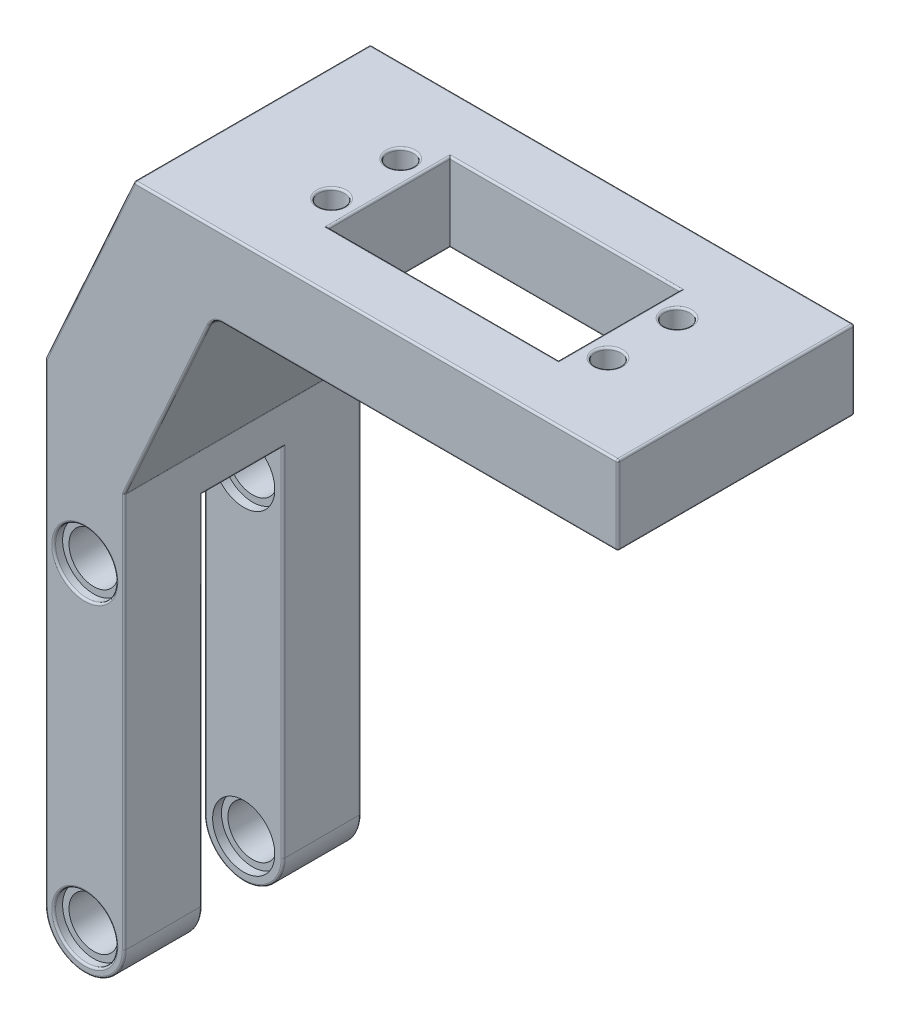
SolidWorks part; units mm, degrees
ref_plane "前视基准面" through (0, 0, 0) normal (0, 0, 1) x (1, 0, 0)
ref_plane "上视基准面" through (0, 0, 0) normal (0, 1, 0) x (1, 0, 0)
ref_plane "右视基准面" through (0, 0, 0) normal (1, 0, 0) x (0, 0, -1)
other "Configuration Table"
sketch "草图1" plane through (0, 0, 0) normal (0, 0, 1) x (1, 0, 0)
  line L1 (-4, -36) -> (4, -36)
  line L2 (-4, -36) -> (-4, 36)
  line L3 (-4, 36) -> (4, 36)
  line L4 (4, -36) -> (4, 36)
  line L5 (-4, -36) -> (4, 36) construction
  line L6 (-4, 36) -> (4, -36) construction
  line L7 (4, 36) -> (54, 36)
  line L8 (4, 36) -> (4, 28)
  line L9 (4, 28) -> (54, 28)
  line L10 (54, 36) -> (54, 28)
  point P0 (0, 0)
  dimension "D1" = 8
  dimension "D2" = 72
  dimension "D3" = 8
  dimension "D4" = 50
extrude "凸台-拉伸1" add sketch "草图1" along normal mid plane 24 contours L1 L4 L3 L2 | L10 L7 L4 L9 region at (0, 0, 0) region at (29, 32, 0)
sketch "草图2" plane through (0, -36, 0) normal (0, -1, 0) x (1, 0, 0)
  line L0 (4, 12) -> (4, -12) construction
  line L1 (-4, -4.1) -> (4, -4.1)
  line L2 (-4, -4.1) -> (-4, 4.1)
  line L3 (-4, 4.1) -> (4, 4.1)
  line L4 (4, -4.1) -> (4, 4.1)
  line L5 (-4, -4.1) -> (4, 4.1) construction
  line L6 (-4, 4.1) -> (4, -4.1) construction
  point P0 (0, 0)
  dimension "D1" = 8.2
extrude "切除-拉伸1" cut sketch "草图2" against normal blind 40.1
sketch "草图3" plane through (0, 0, 0) normal (0, 0, 1) x (1, 0, 0)
  line L0 (-4, -36) -> (4, -36) construction
  circle A0 centre (0, 0) radius 2.5
  circle A1 centre (0, -32) radius 2.5
  dimension "D1" = 5
  dimension "D2" = 4
  dimension "D3" = 32
extrude "切除-拉伸2" cut sketch "草图3" against normal mid plane 40.1
sketch "草图4" plane through (0, 0, 12) normal (0, 0, 1) x (1, 0, 0)
  circle A0 centre (0, 0) radius 3.15
  circle A1 centre (0, -32) radius 3.15
  dimension "D1" = 6.3
extrude "切除-拉伸3" cut sketch "草图4" against normal blind 0.9
extrude "切除-拉伸4" cut sketch "草图4<2>" along normal blind 0.9 from surface starting at face at (2.5, 0, 4.1)
sketch "草图4<2>" plane through (0, 0, 12) normal (0, 0, 1) x (1, 0, 0) same geometry as "草图4"
extrude "切除-拉伸5" cut sketch "草图4<3>" against normal blind 0.9 from surface starting at face at (-2.5, 0, -4.1)
sketch "草图4<3>" plane through (0, 0, 12) normal (0, 0, 1) x (1, 0, 0) same geometry as "草图4"
extrude "切除-拉伸6" cut sketch "草图4<4>" along normal blind 0.9 from surface starting at face at (2.5, 0, -12)
sketch "草图4<4>" plane through (0, 0, 12) normal (0, 0, 1) x (1, 0, 0) same geometry as "草图4"
sketch "草图5" plane through (0, 36, 0) normal (0, 1, 0) x (1, 0, 0)
  line L0 (30.5, 0) -> (24, 0) construction
  line L1 (42.15, -6.15) -> (18.85, -6.15)
  line L2 (42.15, -6.15) -> (42.15, 6.15)
  line L3 (42.15, 6.15) -> (18.85, 6.15)
  line L4 (18.85, -6.15) -> (18.85, 6.15)
  line L5 (42.15, -6.15) -> (18.85, 6.15) construction
  line L6 (42.15, 6.15) -> (18.85, -6.15) construction
  line L7 (-4, -12) -> (-4, 12) construction
  point P0 (30.5, 0)
  dimension "D1" = 23.3
  dimension "D2" = 12.3
  dimension "D3" = 6.5
  dimension "D4" = 6.5
  dimension "D5" = 28
extrude "切除-拉伸7" cut sketch "草图5" against normal blind 8
sketch "草图6" plane through (0, 28, 0) normal (0, -1, 0) x (1, 0, 0)
  line L1 (16.5, 3.5) -> (44.5, 3.5) construction
  line L2 (16.5, 3.5) -> (16.5, -3.5) construction
  line L3 (16.5, -3.5) -> (44.5, -3.5) construction
  line L4 (44.5, 3.5) -> (44.5, -3.5) construction
  line L5 (16.5, 3.5) -> (44.5, -3.5) construction
  line L6 (16.5, -3.5) -> (44.5, 3.5) construction
  circle A0 centre (44.5, 3.5) radius 1.3
  circle A1 centre (44.5, -3.5) radius 1.3
  circle A2 centre (16.5, 3.5) radius 1.3
  circle A3 centre (16.5, -3.5) radius 1.3
  point P0 (30.5, 0)
  dimension "D3" = 2.6
  dimension "D1" = 28
  dimension "D2" = 7
extrude "切除-拉伸8" cut sketch "草图6" against normal blind 8
chamfer "倒角1" distance 20 distance2 9 1 edges at (4, 28, 0) first distance on face at (4, -9.975, 0)
chamfer "倒角2" distance 9 distance2 20 1 edges at (-4, 36, 0) first distance on face at (45.8, 36, -3.5)
fillet "圆角4" radius 1.5 1 edges at (13, 28, 0)
fillet "圆角2" radius 4 4 edges at (-4, -36, 8.05) (4, -36, 8.05) (-4, -36, -8.05) (4, -36, -8.05)
fillet "圆角3" radius 0.2 53 edges at (-4, -13.95, -4.1) (-2.8284, -34.8284, -4.1) (2.8284, -34.8284, -4.1) (-4, -13.95, 4.1) (-2.8284, -34.8284, 4.1) (2.8284, -34.8284, 4.1) (42.15, 28, 0) (30.5, 28, 6.15) (18.85, 28, 0) (30.5, 28, -6.15) (45.8, 28, 3.5) (17.8, 28, -3.5) (17.8, 28, 3.5) (45.8, 28, -3.5) (4, -13.95, -4.1) (4, 4.1, 0) (4, -13.95, 4.1) (54, 28, 0) (54, 36, 0) (30.5, 36, 6.15) (42.15, 36, 0) (30.5, 36, -6.15) (18.85, 36, 0) (45.8, 36, 3.5) (17.8, 36, -3.5) (17.8, 36, 3.5) (45.8, 36, -3.5) (29.5, 36, 12) (54, 32, 12) (33.9849, 28, 12) (4, -12, 12) (2.8284, -34.8284, 12) (-2.8284, -34.8284, 12) (-4, -8, 12) (3.15, -32, 12) (3.15, 0, 12) (4, -12, -12) (33.9849, 28, -12) (54, 32, -12) (29.5, 36, -12) (-4, -8, -12) (-2.8284, -34.8284, -12) (2.8284, -34.8284, -12) (3.15, -32, -12) (3.15, 0, -12) (4, 8, 0) (5, 36, 0) (0.5, 26, 12) (8.301, 17.5578, 12) (8.301, 17.5578, -12) (0.5, 26, -12) (13.1554, 27.7596, 12) (13.1554, 27.7596, -12)
